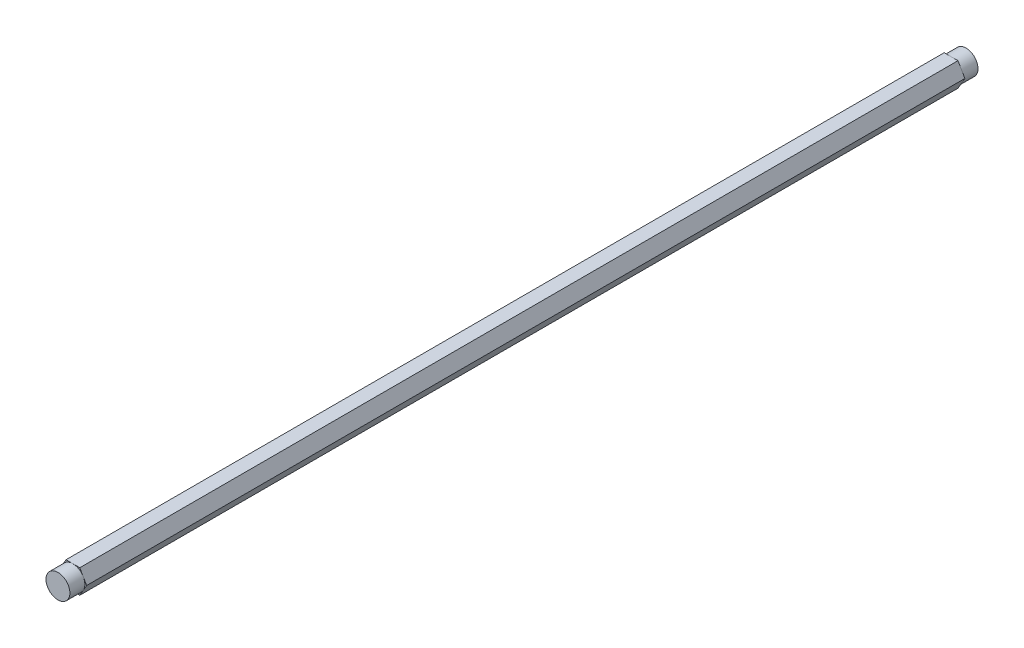
SolidWorks part; units mm, degrees
ref_plane "Front Plane" through (0, 0, 0) normal (0, 0, 1) x (1, 0, 0)
ref_plane "Top Plane" through (0, 0, 0) normal (0, 1, 0) x (1, 0, 0)
ref_plane "Right Plane" through (0, 0, 0) normal (1, 0, 0) x (0, 0, -1)
sketch "Sketch1" plane through (0, 0, 0) normal (0, 0, 1) x (1, 0, 0)
  line L1 (7.3323, 0) -> (3.6662, 6.35)
  line L2 (3.6662, 6.35) -> (-3.6662, 6.35)
  line L3 (-3.6662, 6.35) -> (-7.3323, 0)
  line L4 (-7.3323, 0) -> (-3.6662, -6.35)
  line L5 (-3.6662, -6.35) -> (3.6662, -6.35)
  line L6 (3.6662, -6.35) -> (7.3323, 0)
  circle A0 centre (0, 0) radius 6.35 construction
  dimension "D1" = 12.7
extrude "Boss-Extrude1" add sketch "Sketch1" along normal mid plane 482.6 contours L2 L3 | L1 L2 | L6 L1 | L4 L5 | L3 L4 | L5 L6 region at (0, 0, 0)
sketch "Sketch4" plane through (0, 0, 241.3) normal (0, 0, 1) x (1, 0, 0)
  circle A0 centre (0, 0) radius 6.35
extrude "Cut-Extrude2" cut sketch "Sketch4" against normal blind 7.9502 flip side to cut
mirror "Mirror1" about plane through (0, 0, 0) normal (0, 0, 1) of "Cut-Extrude2"
